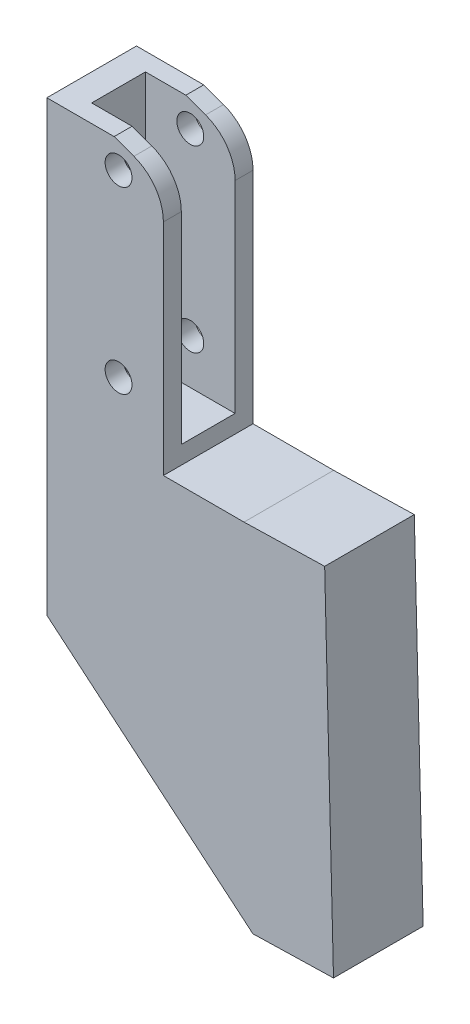
SolidWorks part; units mm, degrees
ref_plane "前视基准面" through (0, 0, 0) normal (0, 0, 1) x (1, 0, 0)
ref_plane "上视基准面" through (0, 0, 0) normal (0, 1, 0) x (1, 0, 0)
ref_plane "右视基准面" through (0, 0, 0) normal (1, 0, 0) x (0, 0, -1)
sketch "草图1" plane through (0, 0, 0) normal (0, 0, 1) x (1, 0, 0)
  line L0 (-6.5, -15) -> (-6.5, -35)
  line L1 (6.5, -15) -> (-6.5, -15)
  line L2 (6.5, -15) -> (6.5, 15)
  line L3 (6.5, 15) -> (-6.5, 15)
  line L4 (-6.5, -15) -> (-6.5, 15)
  line L5 (6.5, -15) -> (-6.5, 15) construction
  line L6 (6.5, 15) -> (-6.5, -15) construction
  line L7 (-6.5, -35) -> (16.4813, -54.2836)
  line L8 (16.4813, -54.2836) -> (15.4956, -15)
  line L9 (15.4956, -15) -> (6.5, -15)
  point P0 (0, 0)
  dimension "D1" = 30
  dimension "D2" = 20
  dimension "D3" = 13
  dimension "D4" = 130
  dimension "D5" = 30
extrude "凸台-拉伸1" add sketch "草图1" along normal blind 10 contours L4 L1 L2 L3 | L8 L9 L1 L0 L7 region at (5.9465, -30.4094, 0) region at (0, 0, 0)
sketch "草图2" plane through (6.5, 0, 0) normal (1, 0, 0) x (0, 0, -1)
  line L0 (-5, 15) -> (-5, -15) construction
  line L1 (-10, 15) -> (0, 15) construction
  line L2 (-10, -15) -> (0, -15) construction
  line L4 (-2, -13) -> (-8, -13)
  line L5 (-2, -13) -> (-2, 15)
  line L6 (-2, 15) -> (-8, 15)
  line L7 (-8, -13) -> (-8, 15)
  line L8 (-2, -13) -> (-8, 15) construction
  line L9 (-2, 15) -> (-8, -13) construction
  point P6 (-5, 1)
  dimension "D1" = 6
  dimension "D2" = 28
extrude "切除-拉伸1" cut sketch "草图2" against normal blind 10
sketch "草图3" plane through (0, 0, 10) normal (0, 0, 1) x (1, 0, 0)
  line L0 (6.5, 15) -> (1.5, 15) construction
  line L1 (6.5, 15) -> (-6.5, 15) construction
  line L2 (1.5, 15) -> (1.5, 12) construction
  circle A0 centre (1.5, 12) radius 1.5
  dimension "D3" = 3
  dimension "D1" = 5
  dimension "D2" = 3
extrude "切除-拉伸2" cut sketch "草图3" against normal through all
sketch "草图4" plane through (0, 0, 10) normal (0, 0, 1) x (1, 0, 0)
  line L0 (1.5, 12) -> (1.5, -8) construction
  circle A0 centre (1.5, -8) radius 1.5
  dimension "D1" = 3
  dimension "D2" = 20
extrude "切除-拉伸3" cut sketch "草图4" against normal through all
chamfer "倒角1" distance 2 angle 70 2 edges at (6.5, 15, 9) (6.5, 15, 1) first distance on face at (6.5, 0.5, 5)
fillet "圆角2" radius 5 2 edges at (6.5, 13, 1) (6.5, 13, 9)
sketch "草图5" plane through (15.1097, 0.3791, 0) normal (0.9997, 0.0251, 0) x (0, 0, -1)
  line L4 (0, -54.68) -> (0, -15.384)
  line L5 (0, -15.384) -> (-10, -15.384)
  line L6 (-10, -15.384) -> (-10, -54.68)
  line L7 (-10, -54.68) -> (0, -54.68)
  line L8 (0, -54.68) -> (0, -15.384)
  line L9 (0, -15.384) -> (-10, -15.384)
  line L10 (-10, -15.384) -> (-10, -54.68)
  line L11 (-10, -54.68) -> (0, -54.68)
  dimension "D1" = 0
extrude "凸台-拉伸2" add sketch "草图5" along normal blind 9
